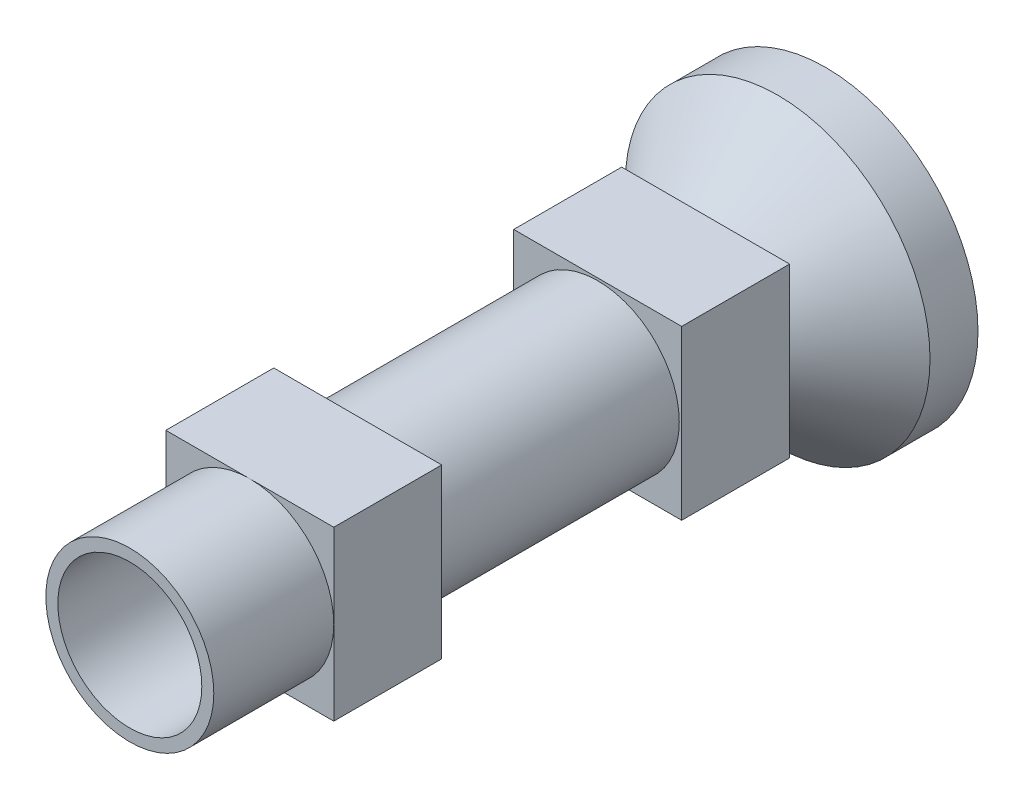
SolidWorks part; units mm, degrees
material "ABS"
ref_plane "正面" through (0, 0, 0) normal (0, 0, 1) x (1, 0, 0)
ref_plane "平面" through (0, 0, 0) normal (0, 1, 0) x (1, 0, 0)
ref_plane "右側面" through (0, 0, 0) normal (1, 0, 0) x (0, 0, -1)
sketch "ｽｹｯﾁ1" plane through (0, 0, 0) normal (0, 0, 1) x (1, 0, 0)
  circle A0 centre (0, 0) radius 3.5 construction
  circle A1 centre (0, 0) radius 6.35
  dimension "D1" = 7
  dimension "D2" = 12.7
ref_plane "平面1" through (0, 0, 5) normal (0, 0, 1) x (1, 0, 0)
sketch "ｽｹｯﾁ2" plane through (0, 0, 5) normal (0, 0, 1) x (1, 0, 0)
  circle A0 centre (0, 0) radius 3.5 construction
  circle A1 centre (0, 0) radius 3.5
ref_plane "平面2" through (0, 0, 29) normal (0, 0, 1) x (1, 0, 0)
ref_plane "平面3" through (0, 0, 24) normal (0, 0, 1) x (1, 0, 0)
sketch "ｽｹｯﾁ5" plane through (0, 0, 29) normal (0, 0, 1) x (1, 0, 0)
  circle A0 centre (0, 0) radius 6.35 construction
  circle A1 centre (0, 0) radius 6.35 construction
  circle A2 centre (0, 0) radius 3.5
  dimension "D1" = 7
extrude "ﾎﾞｽ - 押し出し3" add sketch "ｽｹｯﾁ2" along normal up to surface (19 mm away) contours A1 up to plane "平面3"
extrude "ﾎﾞｽ - 押し出し4" add sketch "ｽｹｯﾁ1" along normal blind 2 separate body
extrude "ﾎﾞｽ - 押し出し5" add sketch "ｽｹｯﾁ5" against normal blind 2
loft "ﾛﾌﾄ1" add section face at (6.35, 0, 2) section face at (3.5, 0, 5) connector at (-0.1759, 6.3476, 2) connector at (-0.0742, 3.4992, 5)
loft "ﾛﾌﾄ2" add section face at (3.5, 0, 24) section face at (3.5, 0, 27) connector at (-0.0749, 3.4992, 24) connector at (-0.0751, 3.4992, 27)
ref_plane "平面5" through (0, 0, 14.5) normal (0, 0, 1) x (1, 0, 0)
ref_plane "平面6" through (0, 0, 15.25) normal (0, 0, 1) x (1, 0, 0)
sketch "ｽｹｯﾁ6" plane through (0, 0, 0) normal (0, 0, -1) x (-1, 0, 0)
  circle A0 centre (0, 0) radius 2.75
  dimension "D1" = 5.5
extrude "ｶｯﾄ - 押し出し1" cut sketch "ｽｹｯﾁ6" against normal blind 3
sketch "ｽｹｯﾁ7" plane through (0, 0, 3) normal (0, 0, -1) x (-1, 0, 0)
  circle A0 centre (0, 0) radius 1.8
  dimension "D1" = 3.6
extrude "ｶｯﾄ - 押し出し2" cut sketch "ｽｹｯﾁ7" against normal through all
sketch "ｽｹｯﾁ8" plane through (0, 0, 29) normal (0, 0, 1) x (1, 0, 0)
  circle A0 centre (0, 0) radius 3
  dimension "D1" = 6
extrude "ｶｯﾄ - 押し出し3" cut sketch "ｽｹｯﾁ8" against normal offset from surface (23 mm away) 3 up to face at (-1.8, 0, 3)
sketch "ｽｹｯﾁ12" plane through (0, 0, 0) normal (0, 0, -1) x (-1, 0, 0)
  line L0 (0, 0) -> (0, 2.75) construction
  line L1 (0, 0) -> (0.3745, 2.7244) construction
  line L2 (0, 0) -> (0.7419, 2.648) construction
  line L3 (0, 0) -> (1.0956, 2.5223) construction
  line L4 (0, 0) -> (1.4289, 2.3497) construction
  line L5 (0, 0) -> (1.7355, 2.1332) construction
  line L6 (0, 0) -> (2.0098, 1.877) construction
  line L7 (0, 0) -> (2.2467, 1.5859) construction
  line L8 (0, 0) -> (2.4417, 1.2652) construction
  line L9 (0, 0) -> (2.5912, 0.9209) construction
  line L10 (0, 0) -> (2.6925, 0.5595) construction
  line L11 (0, 0) -> (2.7436, 0.1877) construction
  line L12 (0, 0) -> (2.7436, -0.1877) construction
  line L13 (0, 0) -> (2.6925, -0.5595) construction
  line L14 (0, 0) -> (2.5912, -0.9209) construction
  line L15 (0, 0) -> (2.4417, -1.2652) construction
  line L16 (0, 0) -> (2.2467, -1.5859) construction
  line L17 (0, 0) -> (2.0098, -1.877) construction
  line L18 (0, 0) -> (1.7355, -2.1332) construction
  line L19 (0, 0) -> (1.4289, -2.3497) construction
  line L20 (0, 0) -> (1.0956, -2.5223) construction
  line L21 (0, 0) -> (0.7419, -2.648) construction
  line L22 (0, 0) -> (0.3745, -2.7244) construction
  line L23 (0, 0) -> (0, -2.75) construction
  line L24 (0, 0) -> (-0.3745, -2.7244) construction
  line L25 (0, 0) -> (-0.7419, -2.648) construction
  line L26 (0, 0) -> (-1.0956, -2.5223) construction
  line L27 (0, 0) -> (-1.4289, -2.3497) construction
  line L28 (0, 0) -> (-1.7355, -2.1332) construction
  line L29 (0, 0) -> (-2.0098, -1.877) construction
  line L30 (0, 0) -> (-2.2467, -1.5859) construction
  line L31 (0, 0) -> (-2.4417, -1.2652) construction
  line L32 (0, 0) -> (-2.5912, -0.9209) construction
  line L33 (0, 0) -> (-2.6925, -0.5595) construction
  line L34 (0, 0) -> (-2.7436, -0.1877) construction
  line L35 (0, 0) -> (-2.7436, 0.1877) construction
  line L36 (0, 0) -> (-2.6925, 0.5595) construction
  line L37 (0, 0) -> (-2.5912, 0.9209) construction
  line L38 (0, 0) -> (-2.4417, 1.2652) construction
  line L39 (0, 0) -> (-2.2467, 1.5859) construction
  line L40 (0, 0) -> (-2.0098, 1.877) construction
  line L41 (0, 0) -> (-1.7355, 2.1332) construction
  line L42 (0, 0) -> (-1.4289, 2.3497) construction
  line L43 (0, 0) -> (-1.0956, 2.5223) construction
  line L44 (0, 0) -> (-0.7419, 2.648) construction
  line L45 (0, 0) -> (-0.3745, 2.7244) construction
  line L46 (0, 0) -> (0.2081, 3.0429) construction
  line L47 (0.2081, 3.0429) -> (-0.0626, 2.7493)
  line L48 (-0.0626, 2.7493) -> (0, 0) construction
  line L49 (0, 0) -> (0.4364, 2.7152) construction
  line L50 (0.4364, 2.7152) -> (0.2081, 3.0429)
  line L51 (1.0214, 2.8739) -> (0.6815, 2.6642)
  line L52 (1.1527, 2.4967) -> (1.0214, 2.8739)
  line L53 (1.7589, 2.4918) -> (1.375, 2.3816)
  line L54 (1.7836, 2.0931) -> (1.7589, 2.4918)
  line L55 (2.3659, 1.9248) -> (1.9666, 1.9223)
  line L56 (2.2822, 1.5343) -> (2.3659, 1.9248)
  line L57 (2.7975, 1.2151) -> (2.4123, 1.3204)
  line L58 (2.6115, 0.8617) -> (2.7975, 1.2151)
  line L59 (3.0216, 0.4153) -> (2.679, 0.6206)
  line L60 (2.7472, 0.1252) -> (3.0216, 0.4153)
  line L61 (3.0216, -0.4153) -> (2.7472, -0.1252)
  line L62 (2.679, -0.6206) -> (3.0216, -0.4153)
  line L63 (2.7975, -1.2151) -> (2.6115, -0.8617)
  line L64 (2.4123, -1.3204) -> (2.7975, -1.2151)
  line L65 (2.3659, -1.9248) -> (2.2822, -1.5343)
  line L66 (1.9666, -1.9223) -> (2.3659, -1.9248)
  line L67 (1.7589, -2.4918) -> (1.7836, -2.0931)
  line L68 (1.375, -2.3816) -> (1.7589, -2.4918)
  line L69 (1.0214, -2.8739) -> (1.1527, -2.4967)
  line L70 (0.6815, -2.6642) -> (1.0214, -2.8739)
  line L71 (0.2081, -3.0429) -> (0.4364, -2.7152)
  line L72 (-0.0626, -2.7493) -> (0.2081, -3.0429)
  line L73 (-0.6205, -2.9862) -> (-0.3123, -2.7322)
  line L74 (-0.802, -2.6304) -> (-0.6205, -2.9862)
  line L75 (-1.4032, -2.708) -> (-1.0379, -2.5466)
  line L76 (-1.482, -2.3165) -> (-1.4032, -2.708)
  line L77 (-2.0818, -2.229) -> (-1.6865, -2.1722)
  line L78 (-2.052, -1.8308) -> (-2.0818, -2.229)
  line L79 (-2.606, -1.5847) -> (-2.21, -1.6366)
  line L80 (-2.4699, -1.2093) -> (-2.606, -1.5847)
  line L81 (-2.9369, -0.8229) -> (-2.5696, -0.9797)
  line L82 (-2.7045, -0.4981) -> (-2.9369, -0.8229)
  line L83 (-3.05, 0) -> (-2.7386, -0.2501)
  line L84 (-2.7386, 0.2501) -> (-3.05, 0)
  line L85 (-2.9369, 0.8229) -> (-2.7045, 0.4981)
  line L86 (-2.5696, 0.9797) -> (-2.9369, 0.8229)
  line L87 (-2.606, 1.5847) -> (-2.4699, 1.2093)
  line L88 (-2.21, 1.6366) -> (-2.606, 1.5847)
  line L89 (-2.0818, 2.229) -> (-2.052, 1.8308)
  line L90 (-1.6865, 2.1722) -> (-2.0818, 2.229)
  line L91 (-1.4032, 2.708) -> (-1.482, 2.3165)
  line L92 (-1.0379, 2.5466) -> (-1.4032, 2.708)
  line L93 (-0.6205, 2.9862) -> (-0.802, 2.6304)
  line L94 (-0.3123, 2.7322) -> (-0.6205, 2.9862)
  circle A0 centre (0, 0) radius 2.75 construction
  circle A1 centre (0, 0) radius 3.05 construction
  arc A2 (0, 2.75) -> (0.3745, 2.7244) centre (0, 0) cw construction
  circle A3 centre (0, 0) radius 2.75 construction
  arc A4 (-0.0626, 2.7493) -> (0.4364, 2.7152) centre (0, 0) cw
  arc A5 (0.6815, 2.6642) -> (1.1527, 2.4967) centre (0, 0) cw
  arc A6 (1.375, 2.3816) -> (1.7836, 2.0931) centre (0, 0) cw
  arc A7 (1.9666, 1.9223) -> (2.2822, 1.5343) centre (0, 0) cw
  arc A8 (2.4123, 1.3204) -> (2.6115, 0.8617) centre (0, 0) cw
  arc A9 (2.679, 0.6206) -> (2.7472, 0.1252) centre (0, 0) cw
  arc A10 (2.7472, -0.1252) -> (2.679, -0.6206) centre (0, 0) cw
  arc A11 (2.6115, -0.8617) -> (2.4123, -1.3204) centre (0, 0) cw
  arc A12 (2.2822, -1.5343) -> (1.9666, -1.9223) centre (0, 0) cw
  arc A13 (1.7836, -2.0931) -> (1.375, -2.3816) centre (0, 0) cw
  arc A14 (1.1527, -2.4967) -> (0.6815, -2.6642) centre (0, 0) cw
  arc A15 (0.4364, -2.7152) -> (-0.0626, -2.7493) centre (0, 0) cw
  arc A16 (-0.3123, -2.7322) -> (-0.802, -2.6304) centre (0, 0) cw
  arc A17 (-1.0379, -2.5466) -> (-1.482, -2.3165) centre (0, 0) cw
  arc A18 (-1.6865, -2.1722) -> (-2.052, -1.8308) centre (0, 0) cw
  arc A19 (-2.21, -1.6366) -> (-2.4699, -1.2093) centre (0, 0) cw
  arc A20 (-2.5696, -0.9797) -> (-2.7045, -0.4981) centre (0, 0) cw
  arc A21 (-2.7386, -0.2501) -> (-2.7386, 0.2501) centre (0, 0) cw
  arc A22 (-2.7045, 0.4981) -> (-2.5696, 0.9797) centre (0, 0) cw
  arc A23 (-2.4699, 1.2093) -> (-2.21, 1.6366) centre (0, 0) cw
  arc A24 (-2.052, 1.8308) -> (-1.6865, 2.1722) centre (0, 0) cw
  arc A25 (-1.482, 2.3165) -> (-1.0379, 2.5466) centre (0, 0) cw
  arc A26 (-0.802, 2.6304) -> (-0.3123, 2.7322) centre (0, 0) cw
  point P53 (0, 0)
  point P54 (0.1877, 2.7436)
  point P56 (0.1877, 2.7436)
  point P129 (0, 0)
  dimension "D2" = 6.1
  dimension "D3" = 10.435
  dimension "D1" = 46
  dimension "D4" = 23
extrude "ｶｯﾄ - 押し出し5" cut sketch "ｽｹｯﾁ12" against normal up to surface (3 mm away) up to face at (-1.8, 0, 3)
sketch "ｽｹｯﾁ14" plane through (0, 0, 24) normal (0, 0, 1) x (1, 0, 0)
  line L1 (3.5, -3.5) -> (-3.5, -3.5)
  line L2 (3.5, -3.5) -> (3.5, 3.5)
  line L3 (3.5, 3.5) -> (-3.5, 3.5)
  line L4 (-3.5, -3.5) -> (-3.5, 3.5)
  line L5 (3.5, -3.5) -> (-3.5, 3.5) construction
  line L6 (3.5, 3.5) -> (-3.5, -3.5) construction
  circle A0 centre (0, 0) radius 3.4
  circle A1 centre (0, 0) radius 3.5 construction
  point P0 (0, 0)
  dimension "D3" = 0.1
  dimension "D1" = 7
  dimension "D2" = 7
extrude "ﾎﾞｽ - 押し出し7" add sketch "ｽｹｯﾁ14" against normal blind 19
sketch "ｽｹｯﾁ16" plane through (0, 0, 14.5) normal (0, 0, 1) x (1, 0, 0)
  line L1 (3.5, -3.5) -> (-3.5, -3.5)
  line L2 (3.5, -3.5) -> (3.5, 3.5)
  line L3 (3.5, 3.5) -> (-3.5, 3.5)
  line L4 (-3.5, -3.5) -> (-3.5, 3.5)
  line L5 (3.5, -3.5) -> (-3.5, 3.5) construction
  line L6 (3.5, 3.5) -> (-3.5, -3.5) construction
  circle A0 centre (0, 0) radius 3.4
  arc A1 (0, 3.5) -> (-3.5, 0) centre (0, 0) ccw construction
  point P0 (0, 0)
  dimension "D1" = 0.1
extrude "ｶｯﾄ - 押し出し6" cut sketch "ｽｹｯﾁ16" against normal blind 5 and the other way blind 5
sketch "ｽｹｯﾁ17" plane through (0, 0, 6) normal (0, 0, 1) x (1, 0, 0)
  circle A0 centre (0, 0) radius 1.8 construction
  circle A1 centre (0, 0) radius 3
  circle A2 centre (0, 0) radius 3
  circle A3 centre (0, 0) radius 1.8
  dimension "D1" = 0
extrude "ﾎﾞｽ - 押し出し8" add sketch "ｽｹｯﾁ17" along normal offset from surface (14 mm away) 9 up to face at (3, 0, 29)
equation "\"D3@ｽｹｯﾁ12\"=360/23*2/3"
